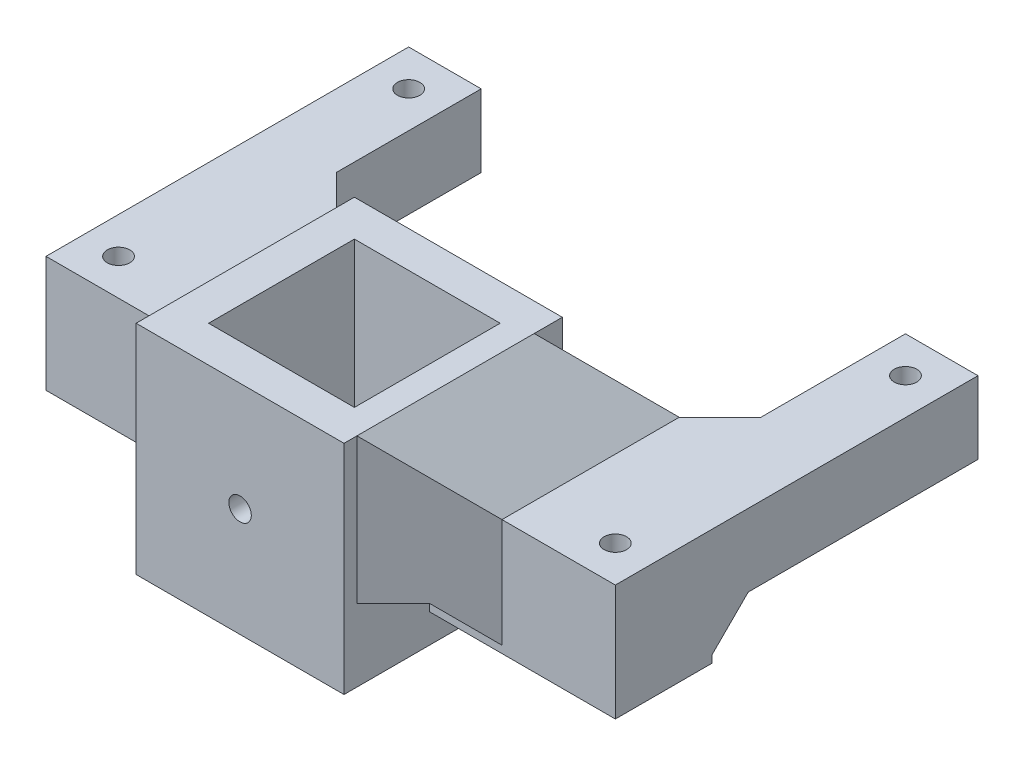
SolidWorks part; units mm, degrees
note: The reader was unsure of these and kept them because the rebuilt part matched: shared geometry of "Sketch2<3>", "Sketch2<5>".
ref_plane "Front Plane" through (0, 0, 0) normal (0, 0, 1) x (1, 0, 0)
ref_plane "Top Plane" through (0, 0, 0) normal (0, 1, 0) x (1, 0, 0)
ref_plane "Right Plane" through (0, 0, 0) normal (1, 0, 0) x (0, 0, -1)
sketch "Sketch1" plane through (0, 0, 0) normal (0, 1, 0) x (1, 0, 0)
  line L0 (0, 0) -> (-20.1, 0) construction
  line L1 (0, 0) -> (80, 0)
  line L2 (0, 0) -> (0, 20.1)
  line L3 (0, 20.1) -> (80, 20.1)
  line L4 (80, 0) -> (80, 20.1)
  line L8 (-20.1, 20.1) -> (-20.1, 0)
  line L9 (-20.1, 20.1) -> (0, 0) construction
  line L10 (-20.1, 20.1) -> (0, 20.1)
  line L11 (-20.1, 20.1) -> (-20.1, 0)
  line L12 (-20.1, 0) -> (0, 0)
  line L13 (0, 20.1) -> (0, 0)
  line L14 (-20.1, 0) -> (0, 20.1) construction
  line L15 (-20.1, 0) -> (-20.1, -80)
  line L16 (0, 0) -> (0, -80)
  line L17 (-20.1, -80) -> (0, -80)
  line L18 (-20.1, 0) -> (0, 0)
  line L19 (-20.1, 20.1) -> (-100.1, 20.1)
  line L20 (-20.1, 0) -> (-100.1, 0)
  line L21 (-100.1, 20.1) -> (-100.1, 0)
  line L22 (-20.1, 20.1) -> (-20.1, 0)
  line L23 (0, 20.1) -> (0, 100.1)
  line L24 (-20.1, 20.1) -> (-20.1, 100.1)
  line L25 (0, 100.1) -> (-20.1, 100.1)
  line L26 (0, 20.1) -> (-20.1, 20.1)
  circle A5 centre (74, 14.1) radius 1.55
  circle A7 centre (74, 6) radius 1.55
  circle A9 centre (-6, -74) radius 1.55
  circle A11 centre (-14.1, -74) radius 1.55
  circle A13 centre (-94.1, 6) radius 1.55
  circle A15 centre (-94.1, 14.1) radius 1.55
  circle A17 centre (-14.1, 94.1) radius 1.55
  circle A19 centre (-6, 94.1) radius 1.55
  point P11 (-10.05, 10.05)
  point P56 (-10.05, 10.05)
  dimension "D4" = 4
  dimension "D11" = 3.1
  dimension "D13" = 3.1
  dimension "D3" = 20.1
  dimension "D5" = 80
  dimension "D24" = 6
  dimension "D25" = 6
  dimension "D26" = 6
  dimension "D27" = 6
sketch "Sketch2" plane through (0, 0, 0) normal (0, 1, 0) x (1, 0, 0)
  line L1 (-49.3, 56.78) -> (-39.3, 56.78)
  line L2 (-49.3, 56.78) -> (-49.3, 6.78)
  line L3 (-49.3, 6.78) -> (-40, 6.78)
  line L9 (19.2, 56.78) -> (29.2, 56.78)
  line L12 (29.2, 56.78) -> (29.2, 6.78)
  line L16 (-20.1, 20.1) -> (0, 20.1) construction
  line L17 (-40, 6.78) -> (29.2, 6.78)
  line L18 (-44.3, 51.78) -> (24.2, 51.78) construction
  line L19 (24.2, 51.78) -> (24.2, 11.78) construction
  line L20 (-10.05, 51.78) -> (-10.05, 20.1) construction
  line L21 (3.5699, 6.78) -> (3.5699, 21.2199)
  line L22 (-40, 40) -> (-40, 0) construction
  line L23 (-49.3, 51.78) -> (-39.3, 51.78) construction
  line L25 (19.2, 51.78) -> (29.2, 51.78) construction
  line L26 (-39.3, 36.85) -> (-22.55, 20.1)
  line L27 (19.2, 36.85) -> (2.45, 20.1)
  line L28 (19.2, 56.78) -> (19.2, 36.85)
  line L29 (-39.3, 56.78) -> (-39.3, 36.85)
  line L30 (-22.55, 20.1) -> (2.45, 20.1)
  line L31 (3.5699, 20.1) -> (29.2, 20.1)
  line L32 (-25.1, 22.65) -> (-25.1, 6.78)
  line L33 (-20.1, 20.1) -> (0, 20.1)
  line L34 (-20.1, 20.1) -> (-20.1, 0)
  line L35 (-20.1, 0) -> (0, 0)
  line L36 (0, 20.1) -> (0, 0)
  line L37 (-25.1, 25.1) -> (3.5699, 25.1)
  line L38 (-25.1, 25.1) -> (-25.1, -5)
  line L39 (-25.1, -5) -> (3.5699, -5)
  line L40 (3.5699, 25.1) -> (3.5699, -5)
  line L41 (-49.3, 20.1) -> (-25.1, 20.1)
  line L42 (-20.1, 20.1) -> (-100.1, 20.1) construction
  line L43 (0, 20.1) -> (80, 20.1) construction
  circle A0 centre (-44.3, 51.78) radius 1.55
  circle A1 centre (24.2, 51.78) radius 1.55
  circle A2 centre (-44.3, 11.78) radius 1.55
  circle A3 centre (24.2, 11.78) radius 1.55
  point P4 (-10.05, 20.1)
  point P16 (24.2, 51.78)
  point P24 (-44.3, 51.78)
  dimension "D4" = 3.1
  dimension "D5" = 3.1
  dimension "D9" = 3.1
  dimension "D13" = 3.1
  dimension "D1" = 68.5
  dimension "D2" = 10
  dimension "D3" = 5
  dimension "D6" = 31.68
  dimension "D7" = 10
  dimension "D8" = 40
  dimension "D10" = 5
  dimension "D11" = 5
  dimension "D12" = 5
  dimension "D14" = 5
  dimension "D15" = 45
  dimension "D16" = 45
  dimension "D17" = 25
  dimension "D18" = 5
  dimension "D19" = 5
  dimension "D20" = 5
  dimension "D21" = 3.5699
extrude "Boss-Extrude3" add sketch "Sketch2" along normal blind 10 from offset 180 contours L2 L41 L32 L26 L29 L1 A0 | L41 L2 L3 L17 L38 A2 | L40 L17 L36 L35 L34 L38 L39 | L34 L30 L26 L32 L38 L17 | L40 L37 L38 L26 L30 L27 | L30 L36 L17 L21 L27 | L31 L21 L17 L12 A3 | L21 L31 L12 L9 L28 L27 A1
extrude "Boss-Extrude4" add sketch "Sketch2<3>" along normal blind 30 from offset 170 contours L26 L38 L17 L34 L30 | L40 L37 L38 L26 L30 L27 | L40 L27 L30 L36 L17 | L40 L17 L36 L35 L34 L38 L39
sketch "Sketch2<3>" plane through (0, 0, 0) normal (0, 1, 0) x (1, 0, 0) same geometry as "Sketch2"
chamfer "Chamfer1" distance 10 angle 45 2 edges at (-25.1, 190, -14.715) (3.5699, 190, -14)
chamfer "Chamfer2" distance 10 angle 45 4 edges at (-30.1, 195, -6.78) (8.5699, 195, -6.78) (3.5699, 190, -6.78) (-25.1, 190, -6.78)
sketch "Sketch3" plane through (0, 0, -25.1) normal (0, 0, -1) x (-1, 0, 0)
  line L0 (-3.5699, 200) -> (25.1, 170) construction
  circle A0 centre (10.765, 185) radius 1.55
  point P7 (10.765, 185)
  dimension "D1" = 3.1
extrude "Cut-Extrude1" cut sketch "Sketch3" against normal blind 43
extrude "Boss-Extrude5" add sketch "Sketch2<5>" along normal blind 6.1 from offset 174 contours L31 L21 L17 L12 A3 | L41 L2 L3 L17 L38 A2
sketch "Sketch2<5>" plane through (0, 0, 0) normal (0, 1, 0) x (1, 0, 0) same geometry as "Sketch2"
chamfer "Chamfer3" distance 5 angle 45 4 edges at (16.385, 180, -20.1) (8.5699, 180, -6.78) (-30.1, 180, -6.78) (-37.2, 180, -20.1)
